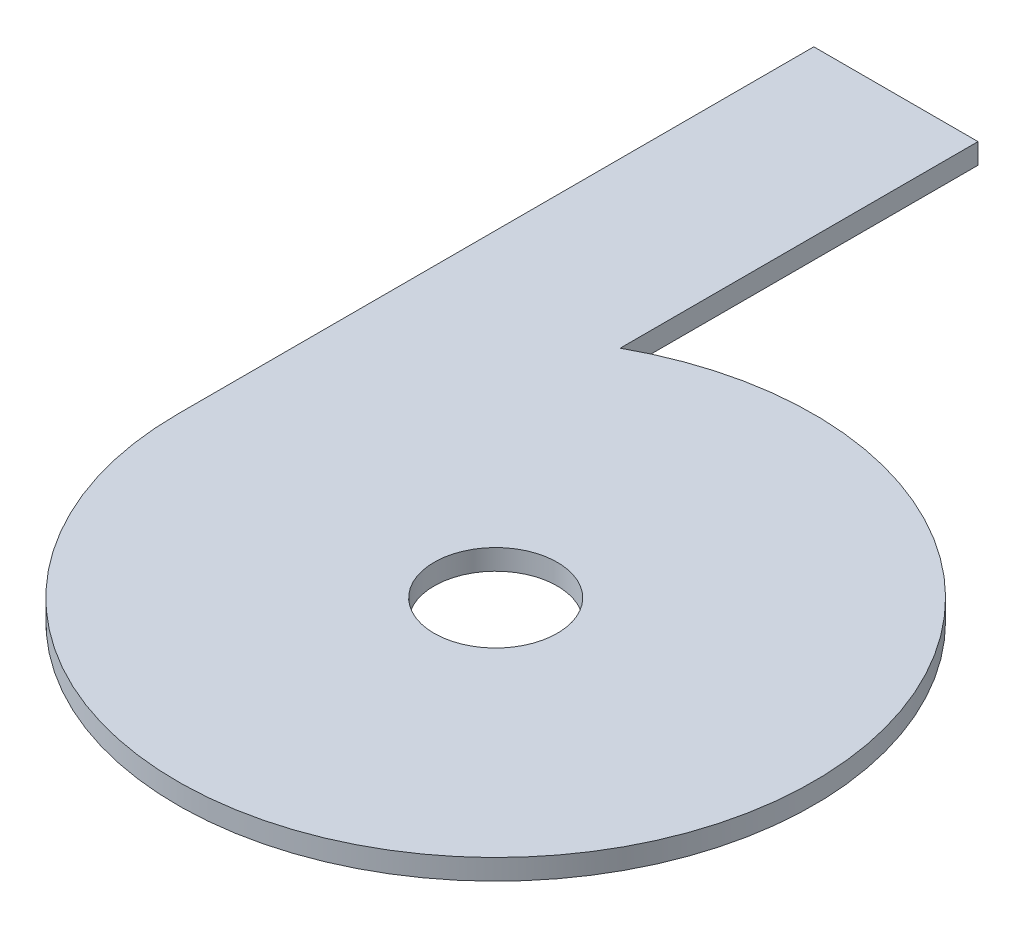
SolidWorks part; units mm, degrees
ref_plane "Front Plane" through (0, 0, 0) normal (0, 0, 1) x (1, 0, 0)
ref_plane "Top Plane" through (0, 0, 0) normal (0, 1, 0) x (1, 0, 0)
ref_plane "Right Plane" through (0, 0, 0) normal (1, 0, 0) x (0, 0, -1)
sketch "Sketch1" plane through (0, 0, 0) normal (0, 1, 0) x (1, 0, 0)
  circle A0 centre (0, 0) radius 31
extrude "Boss-Extrude1" add sketch "Sketch1" along normal blind 2
sketch "Sketch2" plane through (0, 2, 0) normal (0, 1, 0) x (1, 0, 0)
  circle A0 centre (0, 0) radius 6
extrude "Cut-Extrude1" cut sketch "Sketch2" against normal blind 2
sketch "Sketch3" plane through (0, 2, 0) normal (0, 1, 0) x (1, 0, 0)
  line L1 (-31, 0) -> (-15, 0)
  line L2 (-31, 0) -> (-31, 62)
  line L3 (-31, 62) -> (-15, 62)
  line L4 (-15, 0) -> (-15, 62)
  circle A0 centre (0, 0) radius 31 construction
  dimension "D1" = 62
  dimension "D2" = 16
extrude "Boss-Extrude2" add sketch "Sketch3" against normal blind 2
sketch "Sketch4" plane through (0, 2, 0) normal (0, 1, 0) x (1, 0, 0)
  line L3 (-15, 27.1293) -> (-15, 62)
  line L4 (-15, 62) -> (-31, 62)
  line L5 (-31, 62) -> (-31, 0)
  line L6 (-15, 27.1293) -> (-15, 62)
  line L7 (-15, 62) -> (-31, 62)
  line L8 (-31, 62) -> (-31, 0)
  line L10 (-20.007, 48.3271) -> (-20.0089, 61.2271)
  line L11 (-25.907, 48.3262) -> (-20.007, 48.3271)
  line L12 (-25.9089, 61.2262) -> (-25.907, 48.3262)
  line L13 (-20.0089, 61.2271) -> (-25.9089, 61.2262)
  line L14 (-20.007, 48.3271) -> (-20.0089, 61.2271)
  line L15 (-25.907, 48.3262) -> (-20.007, 48.3271)
  line L16 (-25.9089, 61.2262) -> (-25.907, 48.3262)
  line L17 (-20.0089, 61.2271) -> (-25.9089, 61.2262)
  arc A1 (-31, 0) -> (-15, 27.1293) centre (0, 0) ccw
  arc A2 (-31, 0) -> (-15, 27.1293) centre (0, 0) ccw
  dimension "D1" = 0
  dimension "D2" = 0
sketch "Sketch6" plane through (0, 2, 0) normal (0, 1, 0) x (1, 0, 0)
  line L4 (-20.007, 48.3271) -> (-20.0089, 61.2271)
  line L5 (-25.907, 48.3262) -> (-20.007, 48.3271)
  line L6 (-25.9089, 61.2262) -> (-25.907, 48.3262)
  line L7 (-20.0089, 61.2271) -> (-25.9089, 61.2262)
  line L8 (-20.007, 48.3271) -> (-20.0089, 61.2271)
  line L9 (-25.907, 48.3262) -> (-20.007, 48.3271)
  line L10 (-25.9089, 61.2262) -> (-25.907, 48.3262)
  line L11 (-20.0089, 61.2271) -> (-25.9089, 61.2262)
  dimension "D1" = 0
